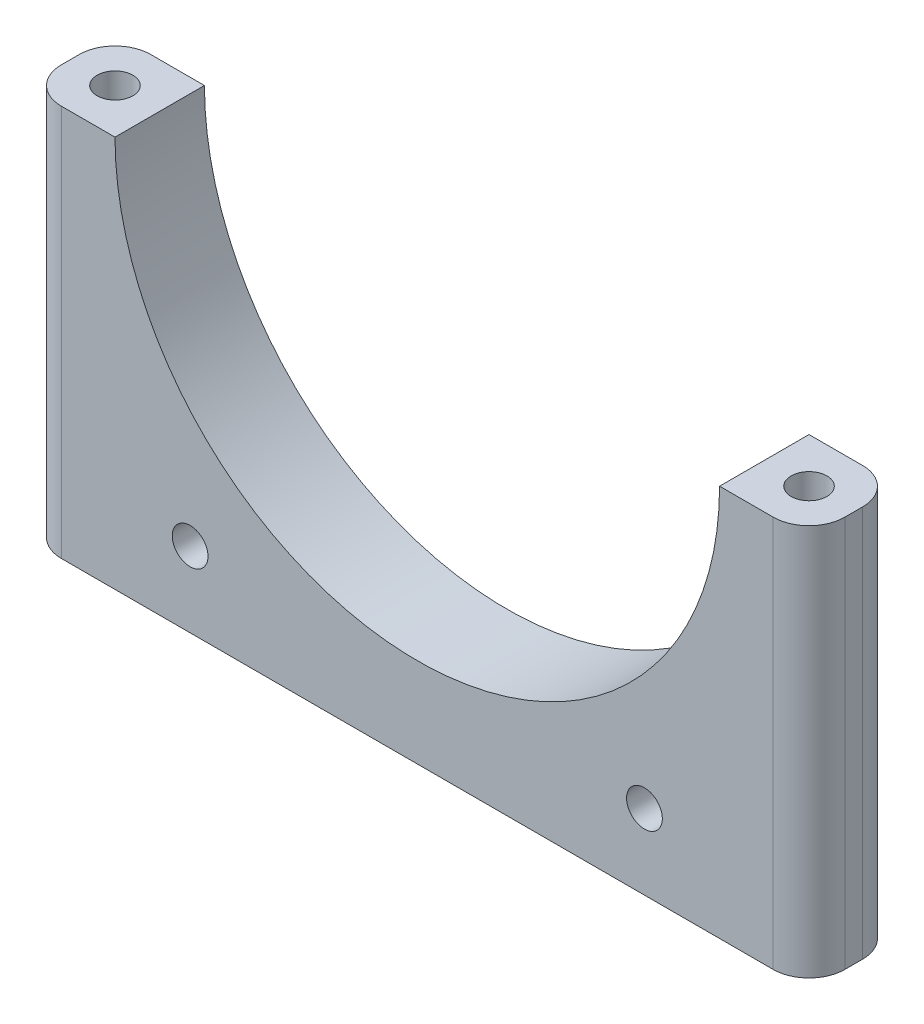
SolidWorks part; units mm, degrees
ref_plane "Front Plane" through (0, 0, 0) normal (0, 0, 1) x (1, 0, 0)
ref_plane "Top Plane" through (0, 0, 0) normal (0, 1, 0) x (1, 0, 0)
ref_plane "Right Plane" through (0, 0, 0) normal (1, 0, 0) x (0, 0, -1)
sketch "Sketch4" plane through (0, 0, 0) normal (0, 0, 1) x (1, 0, 0)
  line L0 (0, 0) -> (0, 169)
  line L1 (-84.5, 84.5) -> (84.5, 84.5)
  line L2 (0, 0) -> (0, 194)
  line L3 (-109.5, 84.5) -> (-109.5, -25)
  line L4 (109.5, 84.5) -> (109.5, -25)
  line L5 (109.5, -25) -> (0, -25)
  line L6 (0, -25) -> (-109.5, -25)
  line L7 (-109.5, 84.5) -> (109.5, 84.5)
  circle A0 centre (0, 84.5) radius 84.5
  circle A1 centre (0, 84.5) radius 109.5
  dimension "D1" = 169
  dimension "D2" = 25
extrude "Boss-Extrude1" add sketch "Sketch4" along normal blind 25 contours A1 L3 L6 | L7 A1 A0 | A1 L5 L4 region at (61.4819, 23.0181, 0) region at (-85.0412, -0.5412, 0) region at (85.0412, -0.5412, 0)
sketch "Sketch5" plane through (0, 84.5, 0) normal (0, 1, 0) x (1, 0, 0)
  line L0 (0, 0) -> (0, -33.3515) construction
  line L1 (-109.5, 0) -> (-84.5, 0) construction
  line L2 (-109.5, -25) -> (-109.5, 0) construction
  circle A0 centre (-97, -12.5) radius 5
  circle A1 centre (97, -12.5) radius 5
  dimension "D1" = 10
  dimension "D2" = 12.5
  dimension "D3" = 12.5
extrude "Cut-Extrude1" cut sketch "Sketch5" against normal blind 5000 contours A0 | A1
sketch "Sketch6" plane through (0, 0, 25) normal (0, 0, 1) x (1, 0, 0)
  line L0 (-84.5, 84.5) -> (-84.5, -25)
  line L1 (109.5, -25) -> (-109.5, -25) construction
  line L2 (-63.5, 28.7506) -> (-63.5, -4)
  line L3 (0, 0) -> (0, -39.0782) construction
  arc A0 (-84.5, 84.5) -> (84.5, 84.5) centre (0, 84.5) ccw construction
  circle A1 centre (-63.5, -4) radius 5
  circle A2 centre (63.5, -4) radius 5
  dimension "D1" = 10
  dimension "D2" = 21
  dimension "D3" = 21
extrude "Cut-Extrude2" cut sketch "Sketch6" against normal blind 5000 contours A1 | A2 region at (-66.9355, -7.4355, 25) region at (63.5, -4, 25)
fillet "Fillet2" radius 10 4 edges at (109.5, 29.75, 25) (109.5, 29.75, 0) (-109.5, 29.75, 25) (-109.5, 29.75, 0)
